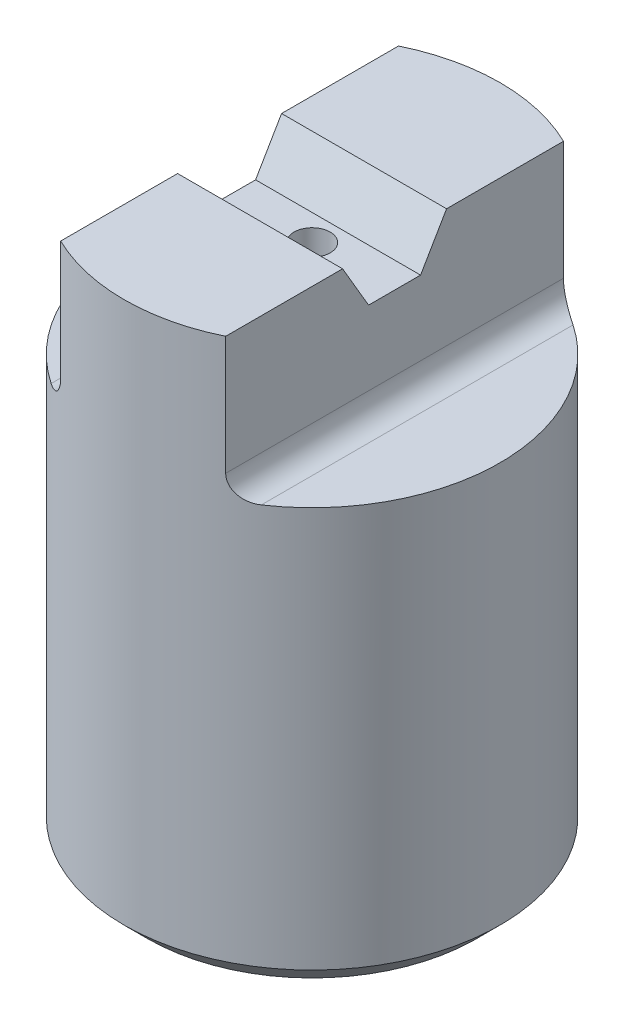
SolidWorks part; units mm, degrees
ref_plane "Alzado" through (0, 0, 0) normal (0, 0, 1) x (1, 0, 0)
ref_plane "Planta" through (0, 0, 0) normal (0, 1, 0) x (1, 0, 0)
ref_plane "Vista lateral" through (0, 0, 0) normal (1, 0, 0) x (0, 0, -1)
sketch "Croquis1" plane through (0, 0, 0) normal (0, 1, 0) x (1, 0, 0)
  circle A0 centre (0, 0) radius 12.6746
  dimension "D1" = 25.3492
extrude "Saliente-Extruir2" add sketch "Croquis1" along normal blind 28.575
sketch "Croquis5" plane through (0, 28.575, 0) normal (0, 1, 0) x (1, 0, 0)
  line L1 (-5.5626, 12.6746) -> (5.5626, 12.6746)
  line L2 (-5.5626, 12.6746) -> (-5.5626, -12.6746)
  line L3 (-5.5626, -12.6746) -> (5.5626, -12.6746)
  line L4 (5.5626, 12.6746) -> (5.5626, -12.6746)
  line L5 (0, -12.6746) -> (0, 12.6746) construction
  line L6 (-5.5626, 0) -> (5.5626, 0) construction
  point P332 (0, 0)
  circle M3 centre (0, 0) radius 12.6746
  dimension "D1" = 11.1252
  dimension "D2" = 25.3492
extrude "Saliente-Extruir3" add sketch "Croquis5" along normal blind 9.525 contours L4 L2 M3 region at (0, 28.575, 0)
sketch "Croquis6" plane through (0, 38.1, 0) normal (0, 1, 0) x (1, 0, 0)
  line L0 (-5.5626, 11.3887) -> (-5.5626, -11.3887) construction
  line L1 (-5.5626, 1.7526) -> (5.5626, 1.7526)
  line L2 (-5.5626, 1.7526) -> (-5.5626, -1.7526)
  line L3 (-5.5626, -1.7526) -> (5.5626, -1.7526)
  line L4 (5.5626, 1.7526) -> (5.5626, -1.7526)
  line L5 (0, -1.7526) -> (0, 1.7526) construction
  line L6 (-5.5626, 0) -> (5.5626, 0) construction
  line L7 (5.5626, 11.3887) -> (5.5626, -11.3887) construction
  point P248 (0, 0)
  dimension "D1" = 3.5052
  dimension "D2" = 11.1252
extrude "Cortar-Extruir3" cut sketch "Croquis6" against normal blind 2.9972
fillet "Redondeo2" radius 1.524 2 edges at (-5.5626, 28.575, 0) (5.5626, 28.575, 0)
chamfer "Chaflán1" distance 1.5748 angle 45 1 edges at (0, 0, 12.6746)
sketch "Croquis15" plane through (5.5626, 0, 0) normal (1, 0, 0) x (0, 0, -1)
  line L0 (-1.7526, 38.1) -> (-3.5052, 38.1)
  line L1 (-1.7526, 38.1) -> (-11.3887, 38.1) construction
  line L2 (-3.5052, 38.1) -> (-1.7526, 35.1028)
  line L3 (-1.7526, 35.1028) -> (-1.7526, 38.1)
extrude "Cortar-Extruir9" cut sketch "Croquis15" against normal through all
sketch "Croquis16" plane through (5.5626, 0, 0) normal (1, 0, 0) x (0, 0, -1)
  line L0 (1.7526, 38.1) -> (3.5052, 38.1)
  line L1 (11.3887, 38.1) -> (1.7526, 38.1) construction
  line L2 (3.5052, 38.1) -> (1.7526, 35.1028)
  line L3 (1.7526, 35.1028) -> (1.7526, 38.1) construction
  line L4 (1.7526, 35.1028) -> (1.7526, 38.1)
extrude "Cortar-Extruir10" cut sketch "Croquis16" against normal through all
sketch "Croquis21" plane through (0, 0, 0) normal (0, -1, 0) x (-1, 0, 0)
  point P0 (0, 0)
sketch "Croquis26" plane through (0, 0, 0) normal (0, -1, 0) x (-1, 0, 0)
  point P0 (0, 0)
sketch "Croquis29" plane through (0, 0, 0) normal (0, -1, 0) x (-1, 0, 0)
  point P0 (0, 0)
sketch "Croquis32" plane through (0, 0, 0) normal (0, -1, 0) x (-1, 0, 0)
  point P0 (0, 0)
sketch "Croquis34" plane through (0, 0, 0) normal (0, -1, 0) x (-1, 0, 0)
  point P0 (0, 0)
sketch "Croquis36" plane through (0, 0, 0) normal (0, -1, 0) x (-1, 0, 0)
  point P0 (0, 0)
sketch "Croquis38" plane through (0, 0, 0) normal (0, -1, 0) x (-1, 0, 0)
  point P0 (0, 0)
hole_wizard "Taladro roscado #8-326" positions "Croquis38" profile "Croquis39" tap size "#8-32" standard "Ansi Inch"
sketch "Croquis39" plane through (0, 0, 0) normal (1, 0, 0) x (0, 0, -1)
  line L0 (0, 0) -> (0, 21.6118)
  line L1 (0, 21.6118) -> (1.7272, 20.574)
  line L2 (1.7272, 20.574) -> (1.7272, 0)
  line L5 (1.7272, 0) -> (0, 0)
  line L10 (0, 21.6118) -> (-1.7272, 20.574) construction
  line L11 (0, -6.35) -> (0, 107.95) construction
  dimension "Diámetro de perforador para roscar" = 3.4544
  dimension "Profundidad de perforador para roscar" = 20.574
  dimension "Ángulo de perforador" = 118
cosmetic thread "Rosca de taladro6" parameters "D1"=8.382, "D2"=4.1656
sketch "Croquis40" plane through (0, 0, 0) normal (0, -1, 0) x (-1, 0, 0)
  circle A0 centre (0, 0) radius 1.2192
  dimension "D1" = 2.4384
extrude "Cortar-Extruir14" cut sketch "Croquis40" against normal through all
sketch "Croquis41" plane through (0, 0, 0) normal (0, -1, 0) x (1, 0, 0)
  text T0 "UT2033" font "Century Gothic" height 3.5
extrude "Cortar-Extruir15" cut sketch "Croquis41" against normal blind 0.0508
